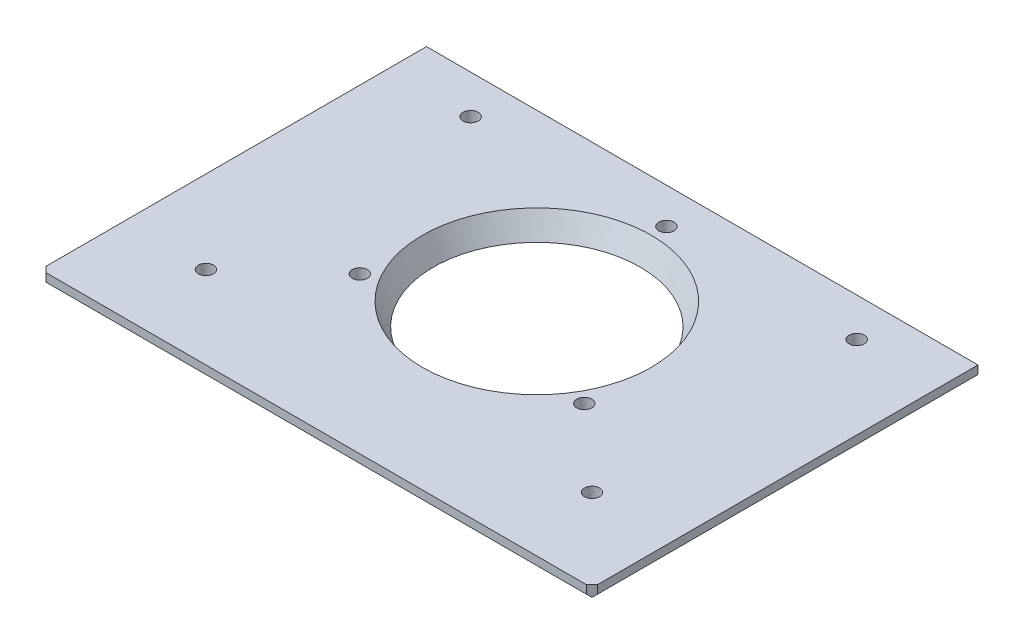
SolidWorks part; units mm, degrees
ref_plane "Front Plane" through (0, 0, 0) normal (0, 0, 1) x (1, 0, 0)
ref_plane "Top Plane" through (0, 0, 0) normal (0, 1, 0) x (1, 0, 0)
ref_plane "Right Plane" through (0, 0, 0) normal (1, 0, 0) x (0, 0, -1)
sketch "Sketch1" plane through (0, 0, 0) normal (0, 1, 0) x (1, 0, 0)
  line L0 (-50, 30) -> (-50, 23)
  line L1 (-50, -30) -> (50, -30)
  line L2 (-50, -30) -> (-50, 30)
  line L3 (-50, 30) -> (50, 30)
  line L4 (50, -30) -> (50, 30)
  line L5 (-50, -30) -> (50, 30) construction
  line L6 (-50, 30) -> (50, -30) construction
  line L7 (-50, -30) -> (50, -30)
  line L8 (-50, -30) -> (-50, -40)
  line L9 (-50, -40) -> (50, -40)
  line L10 (50, -30) -> (50, -40)
  line L11 (-50, 23) -> (-35, 23)
  line L12 (-50, -30) -> (-50, -25)
  line L13 (-50, -25) -> (-35, -25)
  line L14 (50, -30) -> (50, -25)
  line L15 (50, -25) -> (35, -25)
  line L16 (50, 30) -> (50, 23)
  line L17 (50, 23) -> (35, 23)
  circle A0 centre (0, 0) radius 18.75
  arc A1 (0, 23.5) -> (20.3516, -11.75) centre (0, 0) ccw
  circle A5 centre (0, 23.5) radius 1.375
  circle A6 centre (20.3516, -11.75) radius 1.375
  circle A7 centre (-20.3516, -11.75) radius 1.375
  circle A12 centre (-35, 23) radius 1.375
  circle A13 centre (35, 23) radius 1.375
  circle A14 centre (35, -25) radius 1.375
  circle A15 centre (-35, -25) radius 1.375
  point P0 (0, 0)
  point P11 (0, 0)
  dimension "D3" = 10
  dimension "D4" = 37.5
  dimension "D5" = 7
  dimension "D1" = 100
  dimension "D2" = 60
extrude "Boss-Extrude2" add sketch "Sketch1" along normal blind 4 contours L1 L4 L3 L2 A7 A6 A5 A0 | L10 L1 L8 L9 region at (0, 0, -28.8338) region at (0, 0, 35)
chamfer "Chamfer2" distance 2 distance2 4 1 edges at (0, 4, 18.75) first distance on face at (-35, 4, 26.375)
extrude "Boss-Extrude3" add sketch "Sketch1<3>" along normal blind 1 contours A7 | A5 | A6
sketch "Sketch1<3>" plane through (0, 0, 0) normal (0, 1, 0) x (1, 0, 0) same geometry as "Sketch1"
chamfer "Chamfer3" distance 0.5 angle 45 2 edges at (-35, 0, -21.625) (35, 0, -21.625)
chamfer "Chamfer4" distance 1 angle 45 2 edges at (50, 2, 40) (-50, 2, 40)
chamfer "Chamfer5" distance 2.5 angle 45 3 edges at (50, 0, 4.5) (0, 0, 40) (-50, 0, 4.5)
